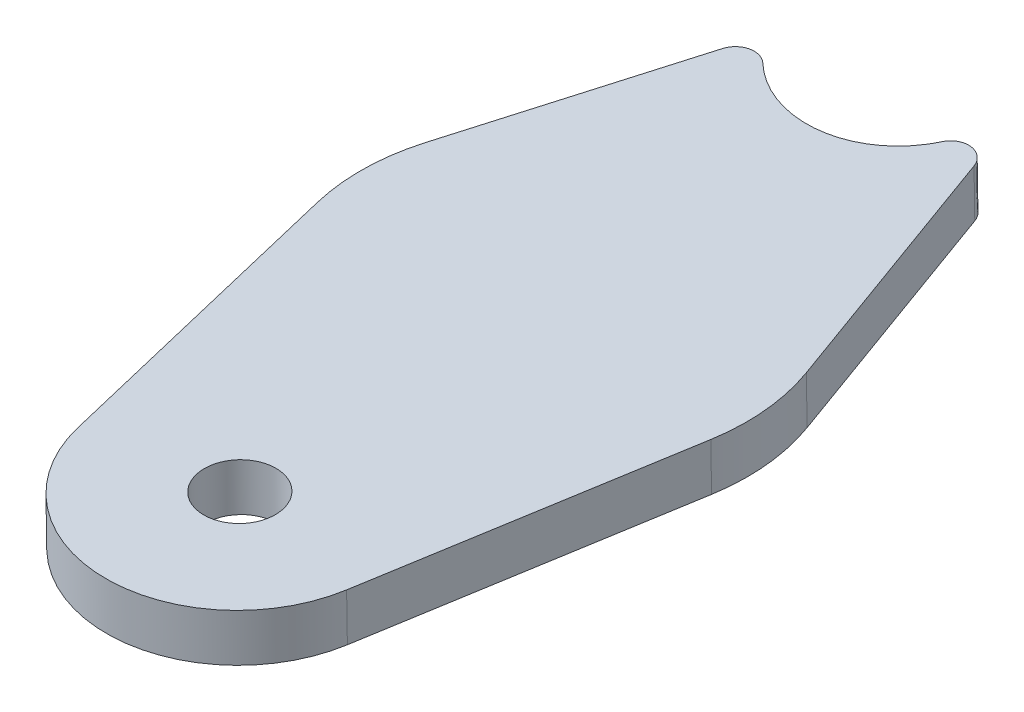
SolidWorks part; units mm, degrees
ref_plane "Front Plane" through (0, 0, 0) normal (0, 0, 1) x (1, 0, 0)
ref_plane "Top Plane" through (0, 0, 0) normal (0, 1, 0) x (1, 0, 0)
ref_plane "Right Plane" through (0, 0, 0) normal (1, 0, 0) x (0, 0, -1)
sketch3d "reference sketch"
  line L9 (16.0505, 95.581, 25.9135) -> (-4.2653, -25.4, -6.8863) construction
  line L10 (-471.6386, -25.4, 282.5992) -> (293.4834, -25.4, -191.3084) construction
  line L11 (0, -25.4, 651.5429) -> (0, 0, 0) construction
  line L12 (0, -25.4, 651.5429) -> (-471.6386, 0, 282.5992) construction
  line L14 (23.8487, 0, 69.5792) -> (-408.0201, 0, 337.0737) construction
ref_plane "pivot plane" through (0, 0, 0) normal (-0.0233, -0.999, -0.0389) x (-0.9997, 0.0233, 0.0009)
ref_plane "Plane3" through (-0.2223, -9.5152, -0.3709) normal (-0.0233, -0.999, -0.0389) x (-0.9997, 0.0233, 0.0009)
sketch "Sketch1" plane through (-0.2223, -9.5152, -0.3709) normal (-0.0233, -0.999, -0.0389) x (-0.9997, 0.0233, 0.0009)
  line L0 (-23.779, -69.5264) -> (408.2154, -336.8178) construction
  line L1 (12.0529, 2.1801) -> (26.7582, -42.1055)
  line L2 (26.7582, -42.1055) -> (17.3505, -87.8106)
  line L3 (0, -1.8222) -> (0, -84.2393) construction
  line L4 (-26.7582, -42.1055) -> (-17.3505, -87.8106)
  line L5 (-12.0529, 2.1801) -> (-26.7582, -42.1055)
  line L6 (12.0529, 2.1801) -> (17.3505, -87.8106) construction
  line L7 (-12.0529, 2.1801) -> (12.0529, 2.1801)
  line L8 (0, -652.0378) -> (0, 0) construction
  circle A0 centre (0, -84.2393) radius 4.7625
  arc A1 (17.3505, -87.8106) -> (-17.3505, -87.8106) centre (0, -84.2393) cw
  arc A2 (-12.0529, 2.1801) -> (12.0529, 2.1801) centre (0, -1.8222) ccw construction
  point P0 (1.3564, 2.1801)
  dimension "D1" = 9.525
  dimension "D2" = 12.7
  dimension "D4" = 12.9517
  dimension "D3" = 15
extrude "Boss-Extrude1" add sketch "Sketch1" along normal blind 6.35
ref_plane "Plane5" through (-4.2653, -25.4, -6.8863) normal (-0.16, -0.9527, -0.2583) x (-0.9871, 0.1544, 0.0419)
sketch "Sketch2" plane through (-4.2653, -25.4, -6.8863) normal (-0.16, -0.9527, -0.2583) x (-0.9871, 0.1544, 0.0419)
  circle A0 centre (0, 0) radius 12.7
  dimension "D1" = 25.4
extrude "Cut-Extrude1" cut sketch "Sketch2" against normal through all
fillet "Fillet1" radius 2.54 2 edges at (-13.7686, -12.3268, 1.6355) (10.7156, -12.8638, -2.6832)
fillet "Fillet3" radius 2.54 1 edges at (11.7533, -12.883, -2.684)
fillet "Fillet2" radius 25.4 2 edges at (-27.0472, -13.7032, 41.6033) (26.4545, -14.951, 41.5547)
sketch "Sketch3" plane through (-0.3704, -15.8586, -0.6182) normal (-0.0233, -0.999, -0.0389) x (-0.4719, -0.0233, 0.8813)
  line L4 (43.0436, 4.8718) -> (13.0837, 10.0458)
  line L5 (85.6018, -26.1549) -> (54.9792, -0.6428)
  line L6 (31.0125, -45.4021) -> (69.2214, -56.7464)
  line L7 (-3.7337, -13.6878) -> (19.8063, -38.5252)
  line L8 (43.0436, 4.8718) -> (13.0837, 10.0458)
  line L9 (85.6018, -26.1549) -> (54.9792, -0.6428)
  line L10 (31.0125, -45.4021) -> (69.2214, -56.7464)
  line L11 (-3.7337, -13.6878) -> (19.8063, -38.5252)
  circle A0 centre (74.2632, -39.7648) radius 4.7625 construction
  circle A1 centre (74.2632, -39.7648) radius 4.7625
  arc A3 (54.9792, -0.6428) -> (43.0436, 4.8718) centre (38.7211, -20.1577) ccw
  arc A4 (69.2214, -56.7464) -> (85.6018, -26.1549) centre (74.2632, -39.7648) ccw
  arc A5 (19.8063, -38.5252) -> (31.0125, -45.4021) centre (38.2419, -21.0527) ccw
  arc A6 (54.9792, -0.6428) -> (43.0436, 4.8718) centre (38.7211, -20.1577) ccw
  arc A7 (69.2214, -56.7464) -> (85.6018, -26.1549) centre (74.2632, -39.7648) ccw
  arc A8 (19.8063, -38.5252) -> (31.0125, -45.4021) centre (38.2419, -21.0527) ccw
  ellipse E1 centre (-2.136, 3.7081) end of major axis (4.4295, -7.6895) minor radius 12.7 (-1.9732, -9.3318) -> (10.1956, 6.8721) ccw
  ellipse E2 centre (-2.136, 3.7081) end of major axis (-8.7015, 15.1056) minor radius 12.7 (-1.9732, -9.3318) -> (10.1956, 6.8721) ccw
  spline S2 degree 3 poles (-159.7532, 1981.73) (272.5428, -1238.303) (41.7058, 3.2377) (-2.9579, -9.497) (-3.1874, -9.6022) (-3.5009, -9.8094) (-3.6014, -9.8877) (-3.7865, -10.0567) (-3.8718, -10.1477) (-4.0282, -10.3428) (-4.0998, -10.4478) (-4.2249, -10.6659) (-4.2785, -10.7788) (-4.4134, -11.1284) (-4.4684, -11.3785) (-4.5036, -11.8767) (-4.4844, -12.1318) (-4.3779, -12.62) (-4.2896, -12.8589) (4.147, -28.6857) (158.7864, 38.861) (-647.431, 1875.0118) knots -22.814809 -22.814809 -22.814809 -22.814809 0.125 0.125 0.25 0.25 0.3125 0.3125 0.375 0.375 0.4375 0.4375 0.5 0.5 0.625 0.625 0.75 0.75 0.875 0.875 9.705486 9.705486 9.705486 9.705486 only from (-1.9732, -9.3318) to (-3.7337, -13.6878)
  spline S3 degree 3 poles (-1.9732, -9.3318) (-2.2262, -9.3272) (-2.4738, -9.359) (-2.9579, -9.497) (-3.1874, -9.6022) (-3.5009, -9.8094) (-3.6014, -9.8877) (-3.7865, -10.0567) (-3.8718, -10.1477) (-4.0282, -10.3428) (-4.0998, -10.4478) (-4.2249, -10.6659) (-4.2785, -10.7788) (-4.4134, -11.1284) (-4.4684, -11.3785) (-4.5036, -11.8767) (-4.4844, -12.1318) (-4.3779, -12.62) (-4.2896, -12.8589) (-4.0541, -13.3007) (-3.907, -13.505) (-3.7337, -13.6878) knots 0 0 0 0 0.125 0.125 0.25 0.25 0.3125 0.3125 0.375 0.375 0.4375 0.4375 0.5 0.5 0.625 0.625 0.75 0.75 0.875 0.875 1 1 1 1
  spline S4 degree 3 poles (76.3771, -1988.5844) (57.4594, -291.4195) (35.3077, 11.8797) (12.2362, 10.0584) (12.0241, 10.0144) (11.6231, 9.8773) (11.4287, 9.7824) (11.0729, 9.549) (10.9114, 9.4117) (10.6223, 9.0947) (10.4998, 8.9205) (10.3007, 8.5453) (10.224, 8.3424) (10.1251, 7.9303) (10.1013, 7.7155) (10.5121, -16.6681) (350.8522, -3.8527) (2004.5418, 151.8601) knots -13.359654 -13.359654 -13.359654 -13.359654 0.125 0.125 0.25 0.25 0.375 0.375 0.5 0.5 0.625 0.625 0.75 0.75 0.875 0.875 15.057395 15.057395 15.057395 15.057395 only from (13.0837, 10.0458) to (10.1956, 6.8721)
  spline S5 degree 3 poles (13.0837, 10.0458) (12.8719, 10.0823) (12.66, 10.0918) (12.2362, 10.0584) (12.0241, 10.0144) (11.6231, 9.8773) (11.4287, 9.7824) (11.0729, 9.549) (10.9114, 9.4117) (10.6223, 9.0947) (10.4998, 8.9205) (10.3007, 8.5453) (10.224, 8.3424) (10.1251, 7.9303) (10.1013, 7.7155) (10.1085, 7.2895) (10.1385, 7.0793) (10.1956, 6.8721) knots 0 0 0 0 0.125 0.125 0.25 0.25 0.375 0.375 0.5 0.5 0.625 0.625 0.75 0.75 0.875 0.875 1 1 1 1
  dimension "D1" = 0
extrude "for DXF, keep suppressed" add sketch "Sketch3" against normal up to surface (6.35 mm away) up to face at (-0.308, -11.0098, 38.0205)
